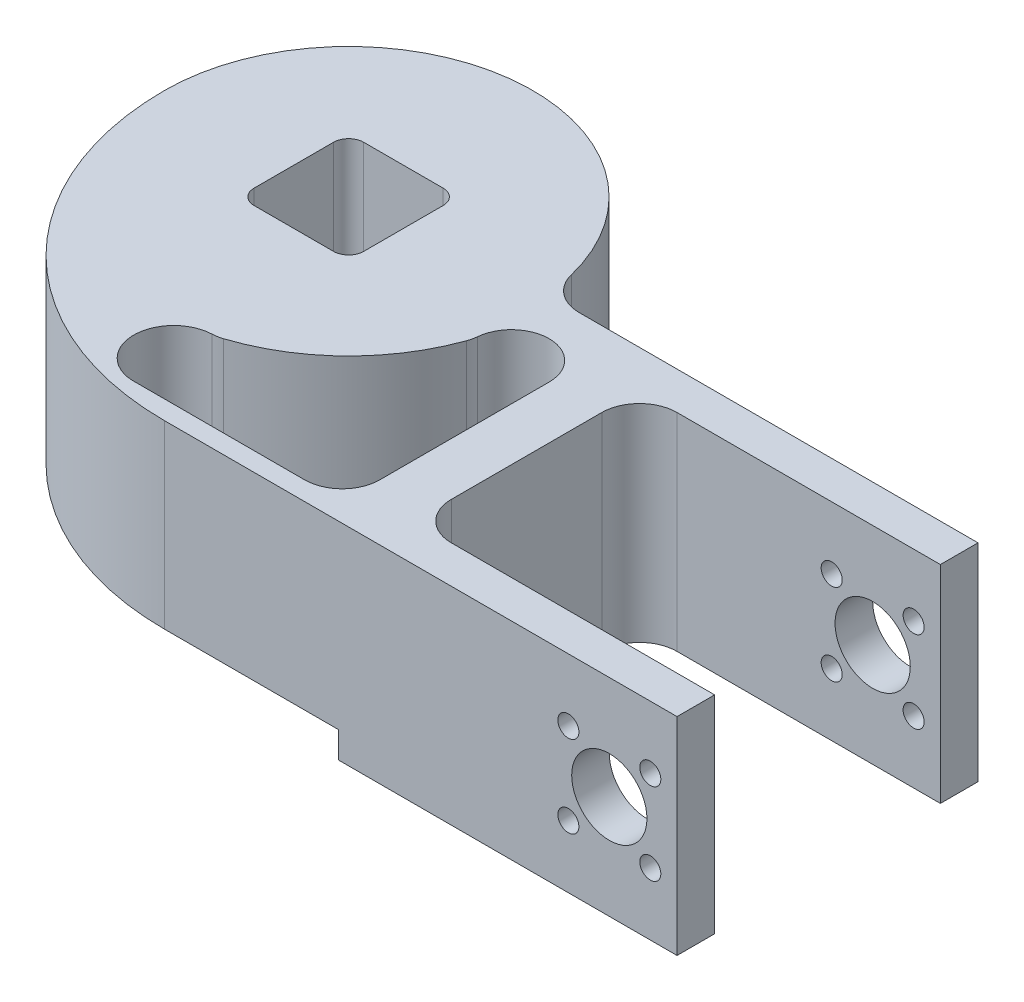
SolidWorks part; units mm, degrees
material "6061-T6 (SS)"
ref_plane "Front Plane" through (0, 0, 0) normal (0, 0, 1) x (1, 0, 0)
ref_plane "Top Plane" through (0, 0, 0) normal (0, 1, 0) x (1, 0, 0)
ref_plane "Right Plane" through (0, 0, 0) normal (1, 0, 0) x (0, 0, -1)
sketch "Sketch1" plane through (0, 0, 0) normal (0, 1, 0) x (1, 0, 0)
  circle A0 centre (0, 0) radius 31.0896
  dimension "D1" = 62.1792
extrude "Boss-Extrude1" add sketch "Sketch1" along normal blind 34.925
sketch "Sketch2" plane through (0, 34.925, 0) normal (0, 1, 0) x (1, 0, 0)
  line L0 (0, 0) -> (-31.0896, 0) construction
  line L1 (0, 0) -> (30.9857, 2.54) construction
  line L2 (46.5427, -48.26) -> (17.1704, -48.26)
  line L4 (46.5427, -48.26) -> (46.5427, 2.54)
  line L7 (30.9857, 2.54) -> (46.5427, 2.54)
  circle A0 centre (0, 0) radius 31.0896 construction
  arc A1 (17.1704, -48.26) -> (-31.0896, 0) centre (17.1704, 0) cw
  circle A2 centre (0, 0) radius 31.0896
  arc A3 (-31.0896, 0) -> (30.9857, 2.54) centre (0, 0) ccw
  dimension "D3" = 2.54
  dimension "D1" = 50.8
  dimension "D2" = 15.557
  dimension "D4" = 0
extrude "Boss-Extrude2" add sketch "Sketch2" against normal blind 30.48
sketch "Sketch3" plane through (0, 34.925, 0) normal (0, 1, 0) x (1, 0, 0)
  line L0 (46.5427, -0.3336) -> (46.5427, -48.26)
  line L1 (17.1704, -48.26) -> (46.5427, -48.26) construction
  line L2 (46.5427, -48.26) -> (103.6927, -48.26)
  line L3 (103.6927, -48.26) -> (103.6927, -41.91)
  line L4 (103.6927, -41.91) -> (52.8927, -41.91)
  line L5 (52.8927, -41.91) -> (52.8927, -3.81)
  line L6 (52.8927, -3.81) -> (103.6927, -3.81)
  line L7 (103.6927, -3.81) -> (103.6927, 2.54)
  line L8 (103.6927, 2.54) -> (46.5427, 2.54)
  line L9 (46.5427, -0.3336) -> (46.5427, 2.54)
  line L10 (46.5427, -48.26) -> (46.5427, 2.54) construction
  dimension "D1" = 57.15
  dimension "D2" = 38.1
  dimension "D3" = 6.35
  dimension "D4" = 6.35
extrude "Boss-Extrude3" add sketch "Sketch3" against normal up to surface (34.925 mm away) up to face at (0, 0, 31.0896)
sketch "Sketch4" plane through (0, 0, -2.54) normal (0, 0, -1) x (-1, 0, 0)
  line L0 (-103.6927, 17.4625) -> (-92.2627, 17.4625) construction
  line L1 (-103.6927, 0) -> (-103.6927, 34.925) construction
  line L2 (-92.2627, 17.4625) -> (-99.1775, 10.5477) construction
  line L3 (-92.2627, 17.4625) -> (-99.1775, 24.3773) construction
  line L4 (-92.2627, 17.4625) -> (-99.1775, 10.5477) construction
  line L5 (-92.2627, 17.4625) -> (-85.3479, 10.5477) construction
  line L6 (-92.2627, 17.4625) -> (-85.3479, 24.3773) construction
  line L8 (-99.1775, 24.3773) -> (-103.6927, 24.3773) construction
  line L9 (-103.6927, 0) -> (-103.6927, 34.925) construction
  line L10 (-99.1775, 10.5477) -> (-103.6927, 10.5477) construction
  circle A0 centre (-92.2627, 17.4625) radius 6.35
  circle A1 centre (-85.3479, 10.5477) radius 1.778
  circle A3 centre (-99.1775, 24.3773) radius 1.778
  circle A4 centre (-99.1775, 10.5477) radius 1.778
  circle A5 centre (-85.3479, 24.3773) radius 1.778
  dimension "D1" = 11.43
  dimension "D2" = 12.7
  dimension "D3" = 3.556
  dimension "D5" = 19.558
  dimension "D4" = 19.558
extrude "Cut-Extrude1" cut sketch "Sketch4" against normal up to surface (50.8 mm away) up to face at (53.3542, 12.7529, 48.26)
sketch "Sketch5" plane through (0, 34.925, 0) normal (0, 1, 0) x (1, 0, 0)
  line L1 (-9.2497, 9.2497) -> (9.2497, 9.2497)
  line L2 (-9.2497, 9.2497) -> (-9.2497, -9.2497)
  line L3 (-9.2497, -9.2497) -> (9.2497, -9.2497)
  line L4 (9.2497, 9.2497) -> (9.2497, -9.2497)
  line L5 (-9.2497, 9.2497) -> (9.2497, -9.2497) construction
  line L6 (-9.2497, -9.2497) -> (9.2497, 9.2497) construction
  point P0 (0, 0)
  dimension "D1" = 26.162
extrude "Cut-Extrude2" cut sketch "Sketch5" against normal up to surface (34.925 mm away) up to face at (0, 0, 31.0896)
fillet "Fillet3" radius 2.54 1 edges at (-9.2497, 17.4625, 9.2497)
fillet "Fillet4" radius 2.54 1 edges at (-9.2497, 17.4625, -9.2497)
fillet "Fillet5" radius 2.54 1 edges at (9.2497, 17.4625, -9.2497)
fillet "Fillet6" radius 2.54 1 edges at (9.2497, 17.4625, 9.2497)
fillet "Fillet8" radius 6.35 1 edges at (30.9857, 19.685, -2.54)
fillet "Fillet9" radius 6.35 1 edges at (52.8927, 17.4625, 41.91)
fillet "Fillet10" radius 6.35 1 edges at (52.8927, 17.4625, 3.81)
sketch "Sketch6" plane through (0, 34.925, 0) normal (0, 1, 0) x (1, 0, 0)
  line L7 (103.6927, 2.54) -> (36.3688, 2.54)
  line L8 (17.1704, -48.26) -> (103.6927, -48.26)
  line L9 (103.6927, -48.26) -> (103.6927, -41.91)
  line L10 (103.6927, -41.91) -> (59.2427, -41.91)
  line L11 (52.8927, -35.56) -> (52.8927, -10.16)
  line L12 (59.2427, -3.81) -> (103.6927, -3.81)
  line L13 (103.6927, -3.81) -> (103.6927, 2.54)
  line L14 (103.6927, 2.54) -> (36.3688, 2.54)
  line L15 (17.1704, -48.26) -> (103.6927, -48.26)
  line L16 (103.6927, -48.26) -> (103.6927, -41.91)
  line L17 (103.6927, -41.91) -> (59.2427, -41.91)
  line L18 (52.8927, -35.56) -> (52.8927, -10.16)
  line L19 (59.2427, -3.81) -> (103.6927, -3.81)
  line L20 (103.6927, -3.81) -> (103.6927, 2.54)
  line L35 (59.2427, -0.635) -> (36.3688, -0.635)
  line L36 (17.1704, -45.085) -> (59.2427, -45.085)
  line L37 (49.7177, -35.56) -> (49.7177, -10.16)
  line L38 (43.6884, -0.635) -> (36.3688, -0.635)
  line L39 (17.1704, -45.085) -> (43.6884, -45.085)
  line L40 (49.7177, -35.56) -> (49.7177, -10.16)
  arc A5 (30.2004, 7.3822) -> (36.3688, 2.54) centre (36.3688, 8.89) ccw
  arc A6 (30.2004, 7.3822) -> (-31.0896, 0) centre (0, 0) ccw
  arc A7 (-31.0896, 0) -> (17.1704, -48.26) centre (17.1704, 0) ccw
  arc A8 (52.8927, -35.56) -> (59.2427, -41.91) centre (59.2427, -35.56) ccw
  arc A9 (59.2427, -3.81) -> (52.8927, -10.16) centre (59.2427, -10.16) ccw
  arc A10 (30.2004, 7.3822) -> (36.3688, 2.54) centre (36.3688, 8.89) ccw
  arc A11 (30.2004, 7.3822) -> (-31.0896, 0) centre (0, 0) ccw
  arc A12 (-31.0896, 0) -> (17.1704, -48.26) centre (17.1704, 0) ccw
  arc A13 (52.8927, -35.56) -> (59.2427, -41.91) centre (59.2427, -35.56) ccw
  arc A14 (59.2427, -3.81) -> (52.8927, -10.16) centre (59.2427, -10.16) ccw
  arc A20 (43.6884, -0.635) -> (49.9101, -8.255) centre (43.6884, -6.985) cw
  arc A21 (43.6884, -45.085) -> (49.9101, -37.465) centre (43.6884, -38.735) ccw
  arc A25 (27.1162, 6.6283) -> (36.3688, -0.635) centre (36.3688, 8.89) ccw
  arc A26 (27.1162, 6.6283) -> (-27.9146, 0) centre (0, 0) ccw
  arc A27 (-27.9146, 0) -> (17.1704, -45.085) centre (17.1704, 0) ccw
  arc A28 (49.7177, -35.56) -> (59.2427, -45.085) centre (59.2427, -35.56) ccw
  arc A29 (59.2427, -0.635) -> (49.7177, -10.16) centre (59.2427, -10.16) ccw
  arc A30 (27.1162, 6.6283) -> (36.3688, -0.635) centre (36.3688, 8.89) ccw
  arc A31 (27.1162, 6.6283) -> (-27.9146, 0) centre (0, 0) ccw
  arc A32 (-27.9146, 0) -> (17.1704, -45.085) centre (17.1704, 0) ccw
  arc A33 (49.7177, -35.56) -> (49.9101, -37.465) centre (59.2427, -35.56) ccw
  arc A34 (49.9101, -8.255) -> (49.7177, -10.16) centre (59.2427, -10.16) ccw
  line M21 (9.2497, 6.7097) -> (9.2497, -6.7097)
  arc M22 (9.2497, -6.7097) -> (6.7097, -9.2497) centre (6.7097, -6.7097) cw
  line M23 (6.7097, -9.2497) -> (-6.7097, -9.2497)
  arc M24 (-6.7097, -9.2497) -> (-9.2497, -6.7097) centre (-6.7097, -6.7097) cw
  line M25 (-9.2497, -6.7097) -> (-9.2497, 6.7097)
  arc M26 (-9.2497, 6.7097) -> (-6.7097, 9.2497) centre (-6.7097, 6.7097) cw
  line M27 (-6.7097, 9.2497) -> (6.7097, 9.2497)
  arc M28 (6.7097, 9.2497) -> (9.2497, 6.7097) centre (6.7097, 6.7097) cw
  dimension "D3" = 6.35
  dimension "D1" = 0
  dimension "D2" = 3.175
extrude "Cut-Extrude3" [suppressed] cut sketch "Sketch6" against normal blind 19.05 contours A34 A20 L38 A30 A31 A32 L39 A21 A33 L40 M28 M21 M22 M23 M24 M25 M26 M27
sketch "Sketch8" [suppressed] plane through (0, 15.875, 0) normal (0, 1, 0) x (1, 0, 0)
  line L1 (35.1127, -2.54) -> (41.4627, -2.54)
  line L2 (28.7627, -8.89) -> (28.7627, -36.83)
  line L3 (47.8127, -8.89) -> (47.8127, -36.83)
  line L6 (35.1127, -43.18) -> (41.4627, -43.18)
  line L7 (103.6927, 2.54) -> (36.3688, 2.54) construction
  line L8 (52.8927, -35.56) -> (52.8927, -10.16) construction
  line L9 (17.1704, -48.26) -> (103.6927, -48.26) construction
  arc A0 (28.7627, -36.83) -> (35.1127, -43.18) centre (35.1127, -36.83) ccw
  arc A1 (47.8127, -36.83) -> (41.4627, -43.18) centre (41.4627, -36.83) cw
  arc A2 (41.4627, -2.54) -> (47.8127, -8.89) centre (41.4627, -8.89) cw
  arc A3 (28.7627, -8.89) -> (35.1127, -2.54) centre (35.1127, -8.89) cw
  dimension "D1" = 6.35
  dimension "D2" = 5.08
  dimension "D3" = 5.08
  dimension "D4" = 19.05
  dimension "D5" = 5.08
extrude "Cut-Extrude4" [suppressed] cut sketch "Sketch8" against normal up to surface (11.43 mm away) up to face at (21.5778, 4.445, 25.8461)
sketch "Sketch9" [suppressed] plane through (0, 15.875, 0) normal (0, 1, 0) x (1, 0, 0)
  line L0 (-9.3373, 19.4097) -> (-9.3373, 18.7747)
  line L1 (-2.9873, 12.4247) -> (3.3627, 12.4247)
  line L2 (9.7127, 18.7747) -> (9.7127, 19.4097)
  line L3 (-2.9873, 25.7597) -> (3.3627, 25.7597)
  line L4 (-6.7097, 9.2497) -> (6.7097, 9.2497) construction
  line L5 (28.7627, -11.8013) -> (28.7627, -8.89) construction
  line L6 (-9.2497, -6.7097) -> (-9.2497, 6.7097) construction
  line L7 (9.2497, 6.7097) -> (9.2497, -6.7097) construction
  line L9 (-9.2497, 0) -> (9.2497, 0) construction
  line L10 (9.7127, -18.7747) -> (9.7127, -19.4097)
  line L11 (-2.9873, -12.4247) -> (3.3627, -12.4247)
  line L12 (-9.3373, -19.4097) -> (-9.3373, -18.7747)
  line L13 (-2.9873, -25.7597) -> (3.3627, -25.7597)
  arc A0 (3.3627, 12.4247) -> (9.7127, 18.7747) centre (3.3627, 18.7747) ccw
  arc A1 (-9.3373, 18.7747) -> (-2.9873, 12.4247) centre (-2.9873, 18.7747) ccw
  arc A2 (-9.3373, 19.4097) -> (-2.9873, 25.7597) centre (-2.9873, 19.4097) cw
  arc A3 (9.7127, 19.4097) -> (3.3627, 25.7597) centre (3.3627, 19.4097) ccw
  arc A4 (3.3627, -12.4247) -> (9.7127, -18.7747) centre (3.3627, -18.7747) cw
  arc A5 (-9.3373, -18.7747) -> (-2.9873, -12.4247) centre (-2.9873, -18.7747) cw
  arc A6 (-9.3373, -19.4097) -> (-2.9873, -25.7597) centre (-2.9873, -19.4097) ccw
  arc A7 (9.7127, -19.4097) -> (3.3627, -25.7597) centre (3.3627, -19.4097) cw
  dimension "D1" = 6.35
  dimension "D2" = 3.175
  dimension "D3" = 16.51
  dimension "D4" = 19.05
  dimension "D5" = 19.05
extrude "Cut-Extrude5" [suppressed] cut sketch "Sketch9" against normal up to surface (11.43 mm away) up to face at (21.5778, 4.445, 25.8461)
sketch "Sketch11" plane through (0, 4.445, 0) normal (0, -1, 0) x (-1, 0, 0)
  line L0 (-44.0027, -10.16) -> (-44.0027, -38.735)
  line L1 (-8.4427, -45.085) -> (-37.6527, -45.085)
  line L2 (-8.4427, -45.085) -> (-8.8214, -38.3416) construction
  line L3 (-8.8214, -38.3416) -> (-9.2001, -31.5981) construction
  line L5 (-17.1704, -48.26) -> (-46.5427, -48.26) construction
  line L6 (-46.5427, -48.26) -> (-46.5427, 2.54) construction
  line L7 (-31.3027, -10.16) -> (-44.0027, -10.16) construction
  arc A0 (-44.0027, -10.16) -> (-31.3322, -9.5481) centre (-37.6527, -10.16) cw
  arc A1 (-44.0027, -38.735) -> (-37.6527, -45.085) centre (-37.6527, -38.735) ccw
  arc A2 (-8.5205, -31.5942) -> (-8.4427, -45.085) centre (-8.8214, -38.3416) cw
  arc A3 (-10.207, -31.2874) -> (-8.5205, -31.5942) centre (-8.2376, -25.2505) ccw
  arc A4 (-30.9916, -11.0728) -> (-10.207, -31.2874) centre (0, 0) ccw
  arc A5 (-31.3322, -9.5481) -> (-30.9916, -11.0728) centre (-25.0118, -8.9363) ccw
  dimension "D1" = 12.7
  dimension "D3" = 3.175
  dimension "D2" = 6.35
  dimension "D5" = 6.7541
  dimension "D7" = 6.35
  dimension "D8" = 6.35
  dimension "D4" = 28.575
  dimension "D6" = 29.21
  dimension "D10" = 2.54
  dimension "D11" = 38.1
extrude "Cut-Extrude6" cut sketch "Sketch11" against normal up to surface (30.48 mm away) up to face at (0, 34.925, 0)
sketch "Sketch12" plane through (0, 0, 0) normal (0, -1, 0) x (1, 0, 0)
  line L0 (0, 0) -> (0, -20.3032) construction
  line L1 (0, 0) -> (0, 20.3032) construction
  line L2 (0, 0) -> (-20.3032, 0) construction
  line L3 (0, 0) -> (20.3032, 0) construction
